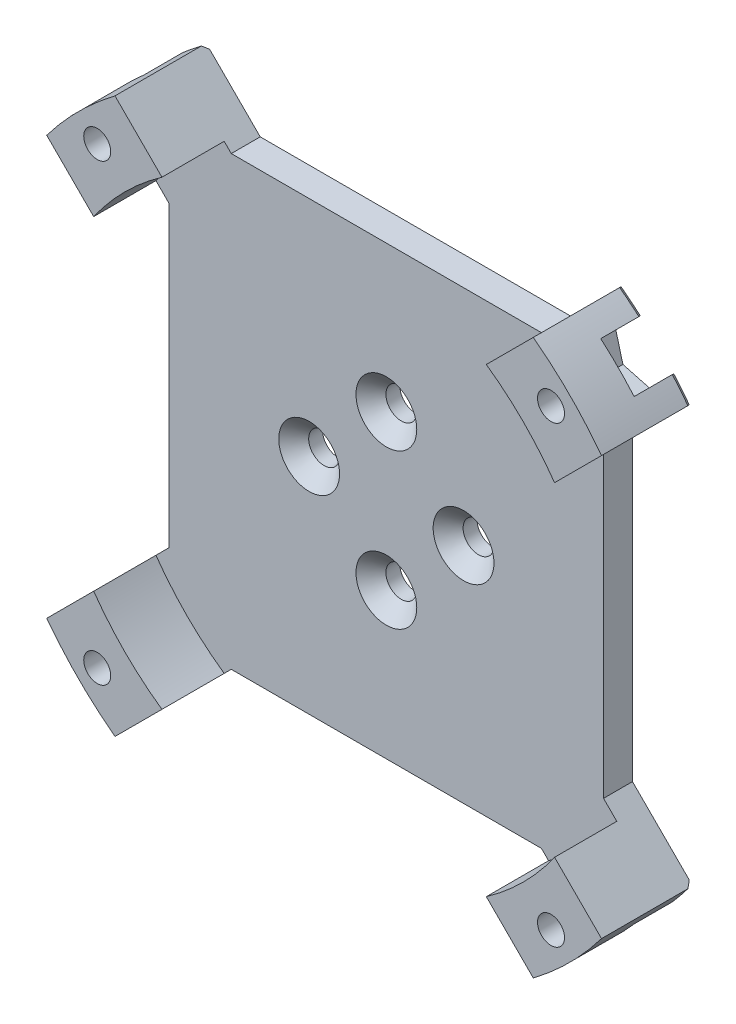
SolidWorks part; units mm, degrees
ref_plane "Front Plane" through (0, 0, 0) normal (0, 0, 1) x (1, 0, 0)
ref_plane "Top Plane" through (0, 0, 0) normal (0, 1, 0) x (1, 0, 0)
ref_plane "Right Plane" through (0, 0, 0) normal (1, 0, 0) x (0, 0, -1)
sketch "Sketch1" plane through (0, 0, 0) normal (0, 0, 1) x (1, 0, 0)
  circle A0 centre (0, 0) radius 36
  circle A1 centre (0, 0) radius 8 construction
  circle A2 centre (0, 8) radius 1.5
  circle A3 centre (8, 0) radius 1.5
  circle A4 centre (0, -8) radius 1.5
  circle A5 centre (-8, 0) radius 1.5
  point P15 (0, 0)
  dimension "D1" = 72
  dimension "D2" = 16
  dimension "D4" = 3
  dimension "D3" = 4
extrude "Boss-Extrude1" add sketch "Sketch1" along normal blind 3 contours A0
hole_wizard "CSK for M3 Flat Head Machine Screw1" positions "Sketch2" profile "Sketch3" countersink size "M3" standard "ANSI Metric" end condition through all
sketch "Sketch2" plane through (0, 0, 3) normal (0, 0, 1) x (1, 0, 0)
  point P3 (0, 8)
  point P6 (-8, 0)
  point P9 (0, -8)
  point P12 (8, 0)
sketch "Sketch3" plane through (0, 8, 3) normal (1, 0, 0) x (0, -1, 0)
  line L0 (0, 0) -> (0, 3)
  line L1 (0, 3) -> (1.6, 3)
  line L2 (1.6, 3) -> (1.6, 1.55)
  line L3 (1.6, 1.55) -> (3.15, 0)
  line L5 (3.15, 0) -> (0, 0)
  line L6 (-1.6, 1.55) -> (-3.15, 0) construction
  line L11 (0, -6.35) -> (0, 107.95) construction
  dimension "Thru Hole Dia." = 3.2
  dimension "Thru Hole Depth" = 3
  dimension "Near C'Sink Dia." = 6.3
  dimension "Near C'Sink Angle" = 90
sketch "Sketch4" plane through (0, 0, 3) normal (0, 0, -1) x (-1, 0, 0)
  line L0 (0, 0) -> (0, 36) construction
  line L1 (0, 0) -> (-25.4558, 25.4558) construction
  circle A0 centre (0, 0) radius 36 construction
  circle A1 centre (0, 0) radius 29.2
  circle A2 centre (0, 0) radius 36
  dimension "D2" = 6.8
  dimension "D1" = 45
extrude "Boss-Extrude2" add sketch "Sketch4" against normal blind 6.45
chamfer "Chamfer1" distance 0.5 angle 45 1 edges at (36, 0, 0)
sketch "Sketch5" plane through (0, 0, 9.45) normal (0, 0, 1) x (1, 0, 0)
  line L0 (0, 0) -> (0, 36) construction
  line L1 (0, 0) -> (-25.4558, 25.4558) construction
  line L2 (-16.0721, 23.1432) -> (-21.6736, 28.7447)
  line L3 (22.5033, -23.1432) -> (-22.5032, -23.1432) construction
  line L4 (22.5033, -23.1432) -> (22.5033, 23.1432) construction
  line L5 (22.5033, 23.1432) -> (-22.5032, 23.1432) construction
  line L6 (-22.5032, -23.1432) -> (-22.5032, 23.1432) construction
  line L7 (22.5033, -23.1432) -> (-22.5032, 23.1432) construction
  line L8 (22.5033, 23.1432) -> (-22.5032, -23.1432) construction
  line L9 (16.0721, 23.1432) -> (21.6736, 28.7447)
  line L10 (-16.0721, 23.1432) -> (16.0721, 23.1432)
  line L11 (0, 0) -> (-36, 0) construction
  line L12 (-28.7447, 21.6736) -> (-22.5032, 15.4322)
  line L13 (-28.7447, -21.6736) -> (-22.5032, -15.4322)
  line L14 (-22.5032, 15.4322) -> (-22.5032, -15.4322)
  line L15 (-16.0721, -23.1432) -> (-21.6736, -28.7447)
  line L16 (-16.0721, -23.1432) -> (16.0721, -23.1432)
  line L17 (16.0721, -23.1432) -> (21.6736, -28.7447)
  line L18 (28.7447, 21.6736) -> (22.5032, 15.4322)
  line L19 (22.5032, 15.4322) -> (22.5032, -15.4322)
  line L20 (28.7447, -21.6736) -> (22.5032, -15.4322)
  circle A0 centre (0, 0) radius 36 construction
  arc A1 (-21.6736, 28.7447) -> (21.6736, 28.7447) centre (0, 0) cw
  arc A2 (-28.7447, 21.6736) -> (-28.7447, -21.6736) centre (0, 0) ccw
  arc A3 (-21.6736, -28.7447) -> (21.6736, -28.7447) centre (0, 0) ccw
  arc A4 (28.7447, 21.6736) -> (28.7447, -21.6736) centre (0, 0) cw
  dimension "D1" = 45
  dimension "D2" = 45.0065
  dimension "D3" = 46.2864
  dimension "D4" = 5
  dimension "D5" = 5
extrude "Cut-Extrude1" cut sketch "Sketch5" against normal through all
sketch "Sketch6" plane through (0, 0, 0) normal (0, 0, -1) x (-1, 0, 0)
  line L0 (0, 0) -> (-25.4558, 25.4558) construction
  line L1 (0, 0) -> (0, 23.1432) construction
  line L2 (16.0721, 23.1432) -> (-16.0721, 23.1432) construction
  line L3 (-26.2439, 22.7791) -> (-27.2441, 23.7793)
  line L4 (-21.5109, 21.5109) -> (-20.7787, 24.2435)
  line L5 (-20.7787, 24.2435) -> (-22.7791, 26.2439)
  line L6 (-22.7791, 26.2439) -> (-25.5117, 25.5117) construction
  line L7 (-25.5117, 25.5117) -> (-26.2439, 22.7791) construction
  line L8 (-26.2439, 22.7791) -> (-24.2435, 20.7787)
  line L9 (-24.2435, 20.7787) -> (-21.5109, 21.5109)
  line L10 (-27.2441, 23.7793) -> (-23.7793, 27.2441)
  line L11 (-23.7793, 27.2441) -> (-22.7791, 26.2439)
  line L12 (27.2441, 23.7793) -> (26.2439, 22.7791)
  line L13 (24.2435, 20.7787) -> (26.2439, 22.7791)
  line L14 (21.5109, 21.5109) -> (24.2435, 20.7787)
  line L15 (20.7787, 24.2435) -> (21.5109, 21.5109)
  line L16 (22.7791, 26.2439) -> (20.7787, 24.2435)
  line L17 (22.7791, 26.2439) -> (23.7793, 27.2441)
  line L18 (23.7793, 27.2441) -> (27.2441, 23.7793)
  line L19 (23.7793, -27.2441) -> (22.7791, -26.2439)
  line L20 (20.7787, -24.2435) -> (22.7791, -26.2439)
  line L21 (21.5109, -21.5109) -> (20.7787, -24.2435)
  line L22 (24.2435, -20.7787) -> (21.5109, -21.5109)
  line L23 (26.2439, -22.7791) -> (24.2435, -20.7787)
  line L24 (26.2439, -22.7791) -> (27.2441, -23.7793)
  line L25 (27.2441, -23.7793) -> (23.7793, -27.2441)
  line L26 (-27.2441, -23.7793) -> (-26.2439, -22.7791)
  line L27 (-24.2435, -20.7787) -> (-26.2439, -22.7791)
  line L28 (-21.5109, -21.5109) -> (-24.2435, -20.7787)
  line L29 (-20.7787, -24.2435) -> (-21.5109, -21.5109)
  line L30 (-22.7791, -26.2439) -> (-20.7787, -24.2435)
  line L31 (-22.7791, -26.2439) -> (-23.7793, -27.2441)
  line L32 (-23.7793, -27.2441) -> (-27.2441, -23.7793)
  arc A0 (-21.6736, 28.7447) -> (-28.7447, 21.6736) centre (0, 0) ccw construction
  circle A1 centre (-23.5113, 23.5113) radius 2.45 construction
  point P43 (0, 0)
  dimension "D1" = 45
  dimension "D2" = 33.25
  dimension "D3" = 4.9
  dimension "D4" = 4
ref_axis "Axis1" through (0, 0, -0.4725) along (0, 0, 1)
sketch "Sketch7" plane through (0, 0, 0) normal (0, 0, -1) x (-1, 0, 0)
  circle A0 centre (-23.5113, 23.5113) radius 1.4
  circle A1 centre (23.5113, 23.5113) radius 1.4
  circle A2 centre (23.5113, -23.5113) radius 1.4
  circle A3 centre (-23.5113, -23.5113) radius 1.4
  point P12 (0, 0)
  dimension "D1" = 2.8
  dimension "D2" = 4
extrude "Cut-Extrude2" cut sketch "Sketch7" against normal through all
extrude "Cut-Extrude3" cut sketch "Sketch6" against normal offset from surface (4.45 mm away) 5 up to face at (22.1113, 23.5113, 9.45)
